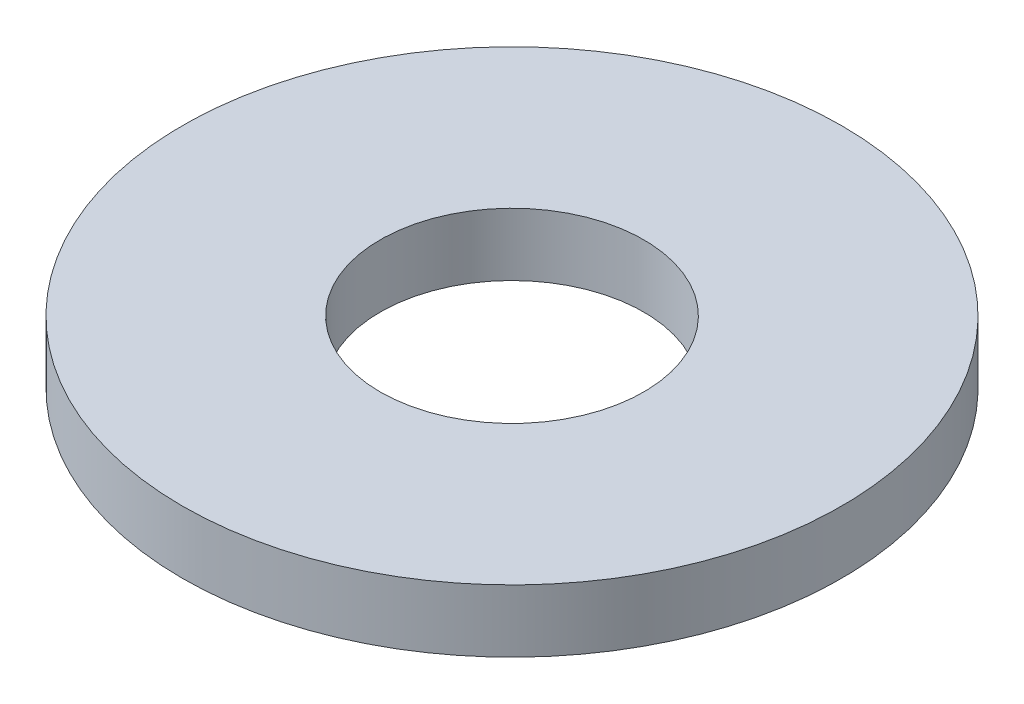
SolidWorks part; units mm, degrees
ref_plane "Front Plane" through (0, 0, 0) normal (0, 0, 1) x (1, 0, 0)
ref_plane "Top Plane" through (0, 0, 0) normal (0, 1, 0) x (1, 0, 0)
ref_plane "Right Plane" through (0, 0, 0) normal (1, 0, 0) x (0, 0, -1)
sketch "Sketch1" plane through (0, 0, 0) normal (0, 1, 0) x (1, 0, 0)
  circle A0 centre (0, 0) radius 100
  dimension "FLANGE_OD" = 200
extrude "Boss-Extrude1" add sketch "Sketch1" along normal blind 19
sketch "Sketch2" plane through (0, 0, 0) normal (0, 1, 0) x (1, 0, 0)
  circle A0 centre (0, 0) radius 40
  dimension "BORE_D" = 80
extrude "Cut-Extrude1" cut sketch "Sketch2" along normal through all
sketch "Sketch3" plane through (0, 19, 0) normal (0, 1, 0) x (1, 0, 0)
  circle A0 centre (0, 0) radius 28.0779 construction
  circle A1 centre (-28.0779, 0) radius 7.3158
  dimension "BOLT_D" = 14.6315
  dimension "BOLT_PCD" = 56.1559
extrude "Cut-Extrude2" cut sketch "Sketch3" against normal blind 17.7589 rebuild error yes
pattern_circular "CirPattern1" count 4 over 360 rebuild error yes
